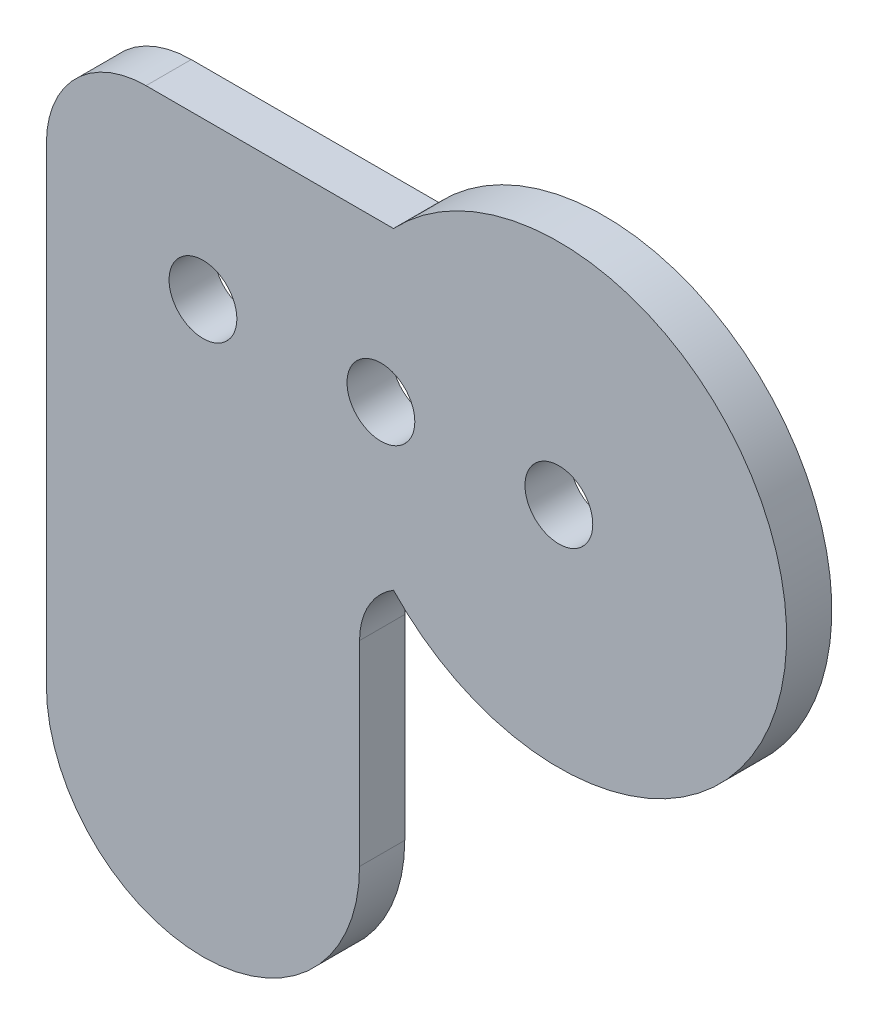
SolidWorks part; units mm, degrees
ref_plane "Front Plane" through (0, 0, 0) normal (0, 0, 1) x (1, 0, 0)
ref_plane "Top Plane" through (0, 0, 0) normal (0, 1, 0) x (1, 0, 0)
ref_plane "Right Plane" through (0, 0, 0) normal (1, 0, 0) x (0, 0, -1)
sketch "Sketch1" plane through (0, 0, 0) normal (0, 0, 1) x (1, 0, 0)
  line L0 (-11.619, 11) -> (-36, 11)
  line L1 (-36, 11) -> (-36, -29)
  line L2 (-14, -29) -> (-14, -11)
  line L3 (-14, -11) -> (-11.619, -11)
  arc A0 (-11.619, -11) -> (-11.619, 11) centre (0, 0) ccw
  arc A1 (-36, -29) -> (-14, -29) centre (-25, -29) ccw
  dimension "D1" = 32
  dimension "D7" = 25
  dimension "D2" = 11
  dimension "D3" = 11
  dimension "D4" = 29
  dimension "D6" = 22
extrude "Boss-Extrude1" add sketch "Sketch1" along normal blind 3.175
fillet "Fillet1" radius 7 1 edges at (-36, 11, 1.5875)
fillet "Fillet2" radius 5 1 edges at (-14, -11, 1.5875)
sketch "Sketch2" plane through (0, 0, 3.175) normal (0, 0, 1) x (1, 0, 0)
  circle A0 centre (0, 0) radius 2.3813
  dimension "D1" = 4.7625
extrude "Cut-Extrude1" cut sketch "Sketch2" against normal through all
pattern_linear "LPattern1" count 3 spacing 12.5 along (-1, 0, 0) of "Cut-Extrude1"
